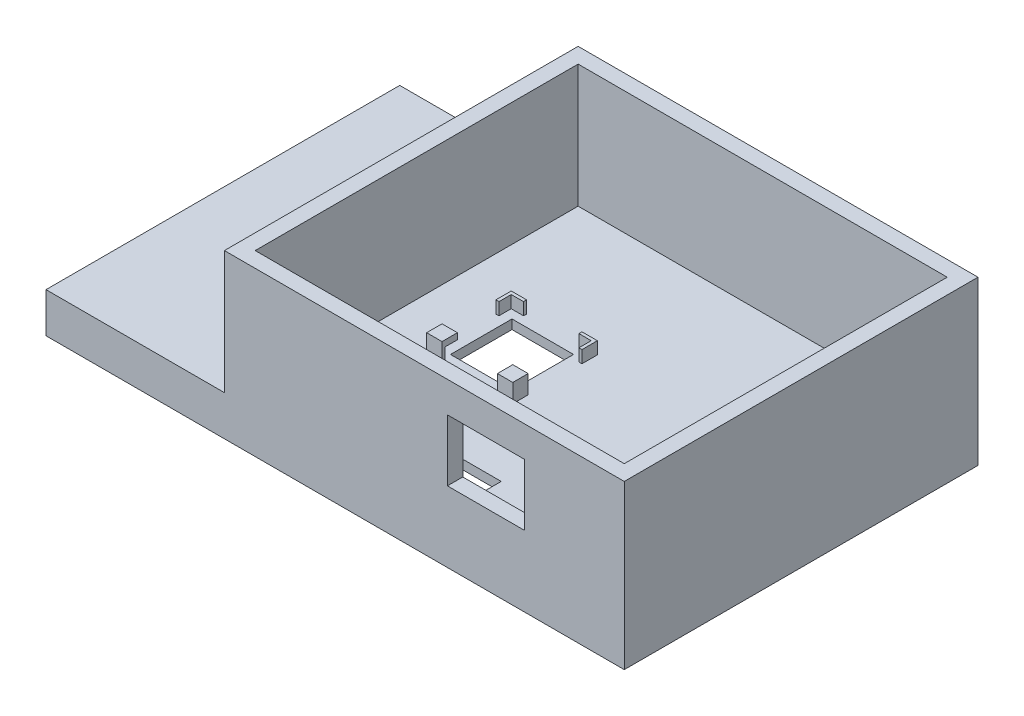
SolidWorks part; units mm, degrees
ref_plane "Front Plane" through (0, 0, 0) normal (0, 0, 1) x (1, 0, 0)
ref_plane "Top Plane" through (0, 0, 0) normal (0, 1, 0) x (1, 0, 0)
ref_plane "Right Plane" through (0, 0, 0) normal (1, 0, 0) x (0, 0, -1)
sketch "Sketch1" plane through (0, 0, 0) normal (0, 1, 0) x (1, 0, 0)
  line L1 (0, 0) -> (188, 0)
  line L2 (0, 0) -> (0, 115)
  line L3 (0, 115) -> (188, 115)
  line L4 (188, 0) -> (188, 115)
  line L5 (5, 5) -> (183, 5)
  line L6 (5, 5) -> (5, 110)
  line L7 (5, 110) -> (183, 110)
  line L8 (183, 5) -> (183, 110)
  dimension "D1" = 5
  dimension "D2" = 5
  dimension "D3" = 5
  dimension "D4" = 5
  dimension "D5" = 178
  dimension "D6" = 105
extrude "Boss-Extrude1" add sketch "Sketch1" along normal blind 10
sketch "Sketch2" plane through (0, 10, 0) normal (0, 1, 0) x (1, 0, 0)
  line L1 (0, 115) -> (188, 115)
  line L2 (0, 115) -> (0, 0)
  line L3 (0, 0) -> (188, 0)
  line L4 (188, 115) -> (188, 0)
extrude "Boss-Extrude2" add sketch "Sketch2" along normal blind 3
sketch "Sketch3" plane through (0, 13, 0) normal (0, 1, 0) x (1, 0, 0)
  line L0 (0, 115) -> (188, 0) construction
  line L1 (188, 115) -> (0, 0) construction
  line L2 (80, 66.25) -> (81, 66.25)
  line L3 (84, 47.5) -> (104, 47.5)
  line L4 (84, 47.5) -> (84, 67.5)
  line L5 (84, 67.5) -> (104, 67.5)
  line L6 (104, 47.5) -> (104, 67.5)
  line L7 (84, 47.5) -> (104, 67.5) construction
  line L8 (84, 67.5) -> (104, 47.5) construction
  line L9 (81, 44.75) -> (85, 44.75)
  line L10 (81, 44.75) -> (81, 48.75)
  line L11 (81, 70.25) -> (85, 70.25)
  line L12 (107, 44.75) -> (107, 48.75)
  line L13 (81, 44.75) -> (107, 70.25) construction
  line L14 (81, 70.25) -> (107, 44.75) construction
  line L15 (80, 43.75) -> (85, 43.75)
  line L16 (80, 43.75) -> (80, 48.75)
  line L17 (80, 71.25) -> (85, 71.25)
  line L18 (108, 43.75) -> (108, 48.75)
  line L19 (80, 43.75) -> (108, 71.25) construction
  line L20 (80, 71.25) -> (108, 43.75) construction
  line L21 (85, 71.25) -> (85, 70.25)
  line L22 (103, 71.25) -> (103, 70.25)
  line L23 (107, 66.25) -> (108, 66.25)
  line L24 (107, 48.75) -> (108, 48.75)
  line L25 (103, 44.75) -> (103, 43.75)
  line L26 (85, 44.75) -> (85, 43.75)
  line L27 (80, 48.75) -> (81, 48.75)
  line L28 (80, 66.25) -> (80, 71.25)
  line L29 (81, 66.25) -> (81, 70.25)
  line L30 (103, 71.25) -> (108, 71.25)
  line L31 (103, 70.25) -> (107, 70.25)
  line L32 (107, 66.25) -> (107, 70.25)
  line L33 (108, 66.25) -> (108, 71.25)
  line L34 (103, 44.75) -> (107, 44.75)
  line L35 (103, 43.75) -> (108, 43.75)
  point P8 (94, 57.5)
  point P13 (94, 57.5)
  point P18 (94, 57.5)
  dimension "D1" = 20
  dimension "D2" = 20
  dimension "D3" = 26
  dimension "D4" = 25.5
  dimension "D5" = 28
  dimension "D6" = 27.5
  dimension "D7" = 5
  dimension "D8" = 5
  dimension "D9" = 5
  dimension "D10" = 5
  dimension "D11" = 5
  dimension "D12" = 5
  dimension "D13" = 5
  dimension "D14" = 5
extrude "Boss-Extrude3" add sketch "Sketch3" along normal blind 4 contours L27 L16 L15 L26 L9 L10 | L2 L29 L11 L21 L17 L28 | L23 L33 L30 L22 L31 L32 | L25 L35 L18 L24 L12 L34 region at (80.0707, 13, -68.75) region at (83, 13, -44.6793) region at (107.0707, 13, -46.75) region at (105.5, 13, -71.1793)
extrude "Cut-Extrude1" cut sketch "Sketch3<3>" against normal up to next contours L3 L6 L5 L4 region at (94, 13, -57.5)
sketch "Sketch3<3>" plane through (0, 13, 0) normal (0, 1, 0) x (1, 0, 0) same geometry as "Sketch3"
sketch "Sketch4" plane through (0, 13, 0) normal (0, 1, 0) x (1, 0, 0)
  line L0 (0, 0) -> (188, 0) construction
  line L1 (188, 115) -> (58, 115)
  line L2 (188, 115) -> (188, 0)
  line L3 (188, 0) -> (58, 0)
  line L4 (58, 115) -> (58, 110)
  line L5 (58, 5) -> (58, 0)
  line L6 (58, 110) -> (183, 110)
  line L8 (58, 5) -> (183, 5)
  line L9 (183, 110) -> (183, 5)
  line L11 (58, 110) -> (63, 110)
  line L12 (58, 110) -> (58, 5)
  line L13 (58, 5) -> (63, 5)
  line L14 (63, 110) -> (63, 5)
  line M19 (0, 0) -> (188, 0)
  line M20 (188, 0) -> (188, 115)
  line M21 (188, 115) -> (0, 115)
  dimension "D1" = 130
  dimension "D2" = 5
  dimension "D3" = 5
  dimension "D4" = 5
  dimension "D5" = 5
extrude "Boss-Extrude4" add sketch "Sketch4" along normal blind 40 contours L14 L6 L12 L8 | L6 L9 L8 L5 L4 M19 M20 M21 region at (186.2643, 13, -57.5) region at (60.5, 13, -57.5)
sketch "Sketch9" plane through (0, 17, 0) normal (0, 1, 0) x (1, 0, 0)
  line L1 (80, 43.75) -> (85, 43.75)
  line L2 (80, 43.75) -> (80, 48.75)
  line L3 (80, 48.75) -> (85, 48.75)
  line L4 (85, 43.75) -> (85, 48.75)
  line L5 (108, 43.75) -> (103, 43.75)
  line L6 (108, 43.75) -> (108, 48.75)
  line L7 (108, 48.75) -> (103, 48.75)
  line L8 (103, 43.75) -> (103, 48.75)
extrude "Boss-Extrude5" add sketch "Sketch9" along normal blind 2
sketch "Sketch10" plane through (0, 13, 0) normal (0, 1, 0) x (1, 0, 0)
  line L0 (63, 5) -> (183, 5) construction
  line L1 (108, 5) -> (128, 5)
  line L2 (108, 5) -> (108, 20)
  line L3 (108, 20) -> (128, 20)
  line L4 (128, 5) -> (128, 20)
  line L5 (183, 110) -> (183, 5) construction
  dimension "D1" = 20
  dimension "D2" = 15
  dimension "D3" = 55
extrude "Cut-Extrude2" cut sketch "Sketch10" against normal up to next
sketch "Sketch11" plane through (0, 0, -5) normal (0, 0, -1) x (-1, 0, 0)
  line L1 (-155.5, 43) -> (-130.5, 43)
  line L2 (-155.5, 43) -> (-155.5, 23)
  line L3 (-155.5, 23) -> (-130.5, 23)
  line L4 (-130.5, 43) -> (-130.5, 23)
  line L5 (-183, 53) -> (-183, 13) construction
  line L6 (-63, 53) -> (-183, 53) construction
  point P4 (0, 0)
  point P8 (0, 0)
  dimension "D1" = 27.5
  dimension "D2" = 20
  dimension "D3" = 25
  dimension "D4" = 10
extrude "Cut-Extrude3" cut sketch "Sketch11" against normal up to next
